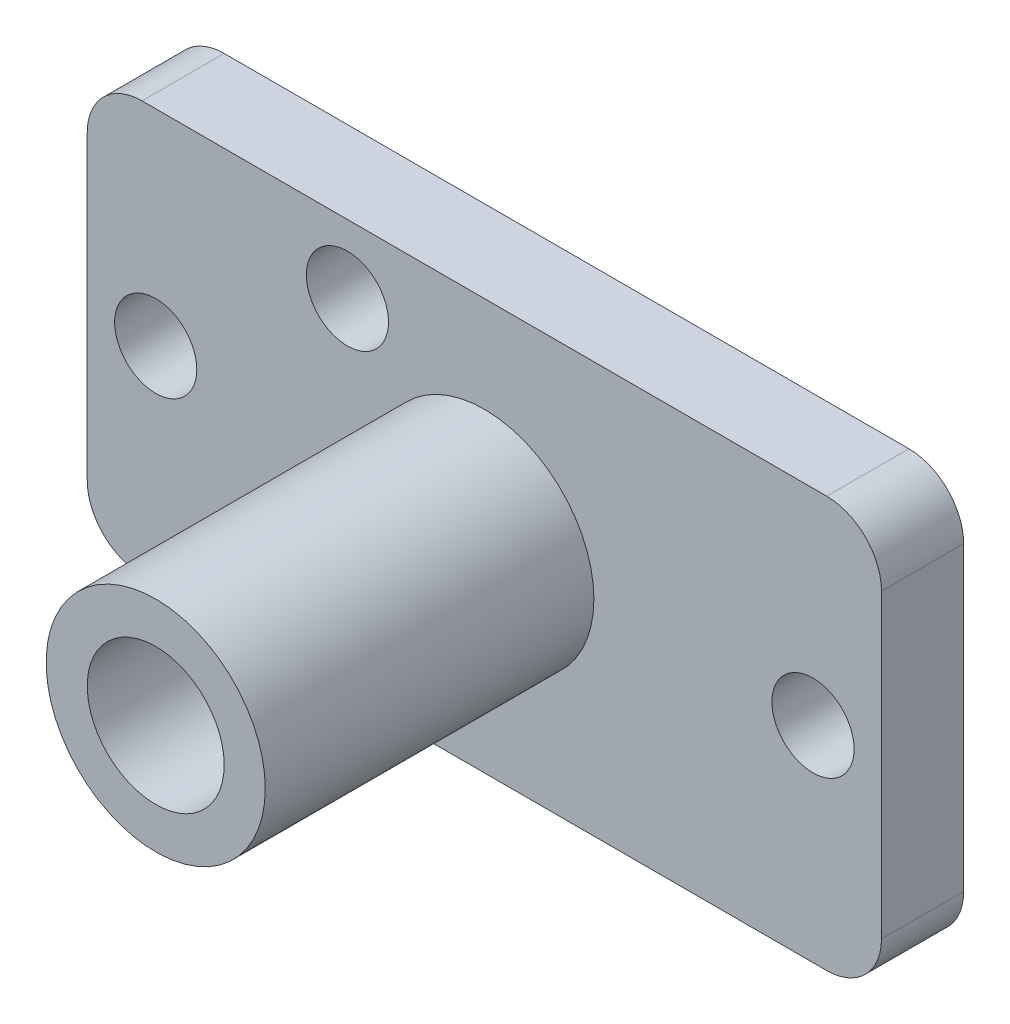
SolidWorks part; units mm, degrees
note: The reader was unsure of these and kept them because the rebuilt part matched: shared geometry of "草图1<3>".
ref_plane "前视基准面" through (0, 0, 0) normal (0, 0, 1) x (1, 0, 0)
ref_plane "上视基准面" through (0, 0, 0) normal (0, 1, 0) x (1, 0, 0)
ref_plane "右视基准面" through (0, 0, 0) normal (1, 0, 0) x (0, 0, -1)
other "Configuration Table"
sketch "草图1" plane through (0, 0, 0) normal (0, 0, 1) x (1, 0, 0)
  line L1 (0, 0) -> (29, 0)
  line L2 (0, 0) -> (0, 15)
  line L3 (0, 15) -> (29, 15)
  line L4 (29, 0) -> (29, 15)
  circle A0 centre (14.5, 7.5) radius 2.5
  circle A1 centre (2.5, 7.5) radius 1.5
  circle A2 centre (26.5, 7.5) radius 1.5
  circle A3 centre (9.5, 12.5) radius 1.5
  circle A4 centre (9.5, 2.5) radius 1.5
  point P8 (29, 7.5)
  point P10 (14.5, 0)
  point P17 (0, 0)
  dimension "D3" = 5
  dimension "D4" = 3
  dimension "D1" = 29
  dimension "D2" = 15
  dimension "D5" = 12
  dimension "D6" = 12
  dimension "D7" = 7
  dimension "D8" = 10
  dimension "D9" = 2.5
extrude "凸台-拉伸1" add sketch "草图1" along normal blind 3 contours L1 L4 L3 L2 A4 A3 A2 A1 A0 | A0
extrude "拉伸-薄壁1" add sketch "草图1<3>" along normal blind 15 thin contours A0
sketch "草图1<3>" plane through (0, 0, 0) normal (0, 0, 1) x (1, 0, 0) same geometry as "草图1"
fillet "圆角1" radius 2 4 edges at (29, 15, 1.5) (29, 0, 1.5) (0, 0, 1.5) (0, 15, 1.5)
